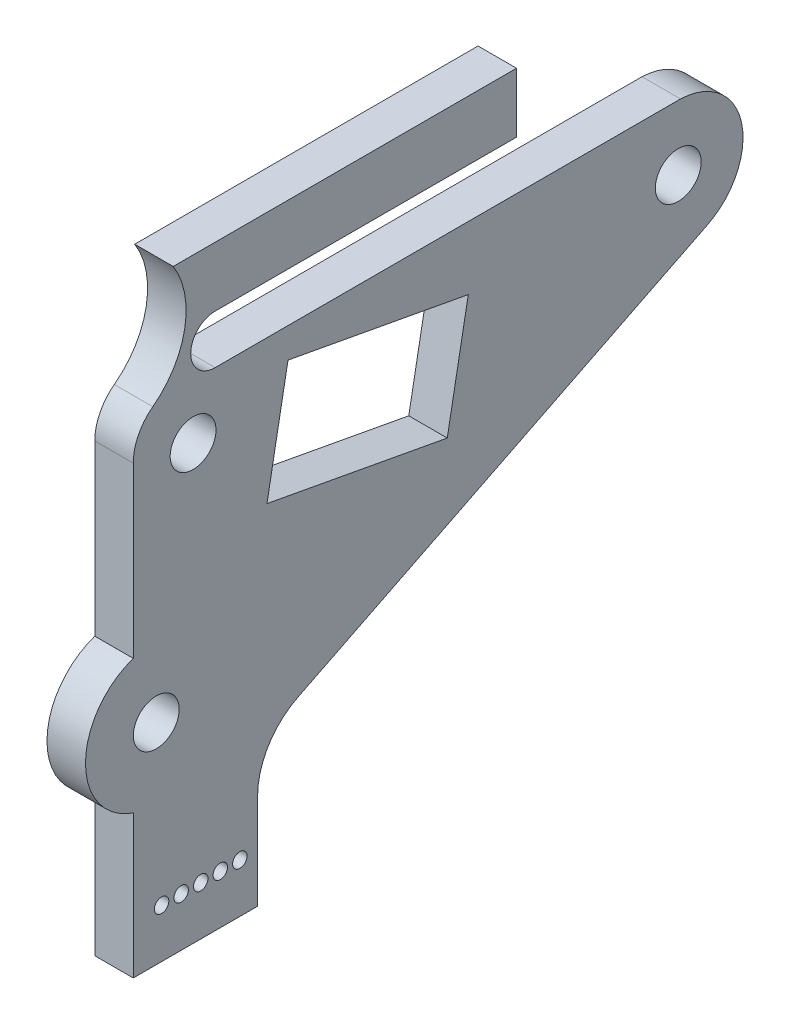
SolidWorks part; units mm, degrees
material "Hardboard"
ref_plane "Front Plane" through (0, 0, 0) normal (0, 0, 1) x (1, 0, 0)
ref_plane "Top Plane" through (0, 0, 0) normal (0, 1, 0) x (1, 0, 0)
ref_plane "Right Plane" through (0, 0, 0) normal (1, 0, 0) x (0, 0, -1)
sketch "Sketch1" plane through (0, 0, 0) normal (1, 0, 0) x (0, 0, -1)
  line L0 (-56.6254, 5.3138) -> (-52.4758, 5.3138) construction
  line L1 (-56.6254, 2.387) -> (-56.6254, -15.1828)
  line L2 (-56.6254, -43.9437) -> (-43.7075, -43.9437)
  line L3 (-43.7075, -43.9437) -> (-43.7075, -34.0304)
  line L4 (-43.7075, -20.39) -> (-25.8088, -20.39) construction
  line L5 (6.73, -20.39) -> (6.73, 6.726) construction
  line L6 (0.2329, 6.726) -> (0, 0) construction
  line L7 (6.73, 0) -> (0, 0) construction
  line L8 (-40.5479, 3.6124) -> (-21.8156, 0.1475)
  line L9 (-40.5479, 3.6124) -> (-42.7334, -8.2033)
  line L10 (-21.8156, 0.1475) -> (-24.0012, -11.6682)
  line L11 (-42.7334, -8.2033) -> (-24.0012, -11.6682)
  line L12 (-45.5531, -38.8637) -> (-47.5851, -38.8637) construction
  line L13 (-48.1168, 11.806) -> (-16.804, 11.806)
  line L14 (-16.804, 11.806) -> (-16.804, 18.009)
  line L15 (-16.804, 18.009) -> (-52.4758, 18.009)
  line L16 (-52.4758, 18.009) -> (-52.4758, 5.3138) construction
  line L17 (-48.1168, 6.726) -> (0.2329, 6.726)
  line L18 (-35.6476, 24.9853) -> (-26.9193, 34.2106) construction
  line L19 (0.2329, 6.726) -> (6.73, 6.726) construction
  line L20 (-25.8088, -20.39) -> (6.73, -20.39) construction
  line L21 (-25.8088, -20.39) -> (3.0033, -6.0227)
  line L22 (-25.8088, -20.39) -> (-39.488, -27.2112)
  line L23 (-43.7075, -29.3153) -> (-43.7075, -20.39) construction
  line L24 (-56.6254, -15.1828) -> (-56.6254, -29.0916) construction
  line L25 (-56.6254, -29.0916) -> (-56.6254, -43.9437)
  circle A0 centre (0, 0) radius 2.3813
  circle A1 centre (-45.5531, -38.8637) radius 0.75
  circle A2 centre (-47.5851, -38.8637) radius 0.75
  circle A3 centre (-49.6171, -38.8637) radius 0.75
  circle A4 centre (-51.6491, -38.8637) radius 0.75
  circle A5 centre (-54.2362, -22.1372) radius 2.3812
  circle A6 centre (-50.4101, 1.0794) radius 2.3812
  circle A7 centre (-53.6811, -38.8637) radius 0.75
  arc A8 (-48.1168, 6.726) -> (-48.1168, 11.806) centre (-48.1168, 9.266) cw
  arc A9 (-52.4758, 18.009) -> (-54.597, 6.4483) centre (-59.8045, 13.3788) cw
  arc A10 (0.2329, 6.726) -> (3.0033, -6.0227) centre (0, 0) cw
  arc A11 (-43.7075, -34.0304) -> (-39.488, -27.2112) centre (-36.0875, -34.0304) cw
  arc A12 (-56.6254, 2.387) -> (-54.597, 6.4483) centre (-51.5454, 2.387) cw
  arc A13 (-56.6254, -15.1828) -> (-56.6254, -29.0916) centre (-54.2362, -22.1372) ccw
  dimension "D1" = 4.7625
  dimension "D2" = 1.5
  dimension "D9" = 7.62
  dimension "D10" = 5.08
  dimension "D3" = 5.08
  dimension "D5" = 2.032
  dimension "D6" = 19.05
  dimension "D7" = 6.203
  dimension "D8" = 5.08
  dimension "D4" = 5
extrude "Boss-Extrude1" add sketch "Sketch1" along normal mid plane 4
